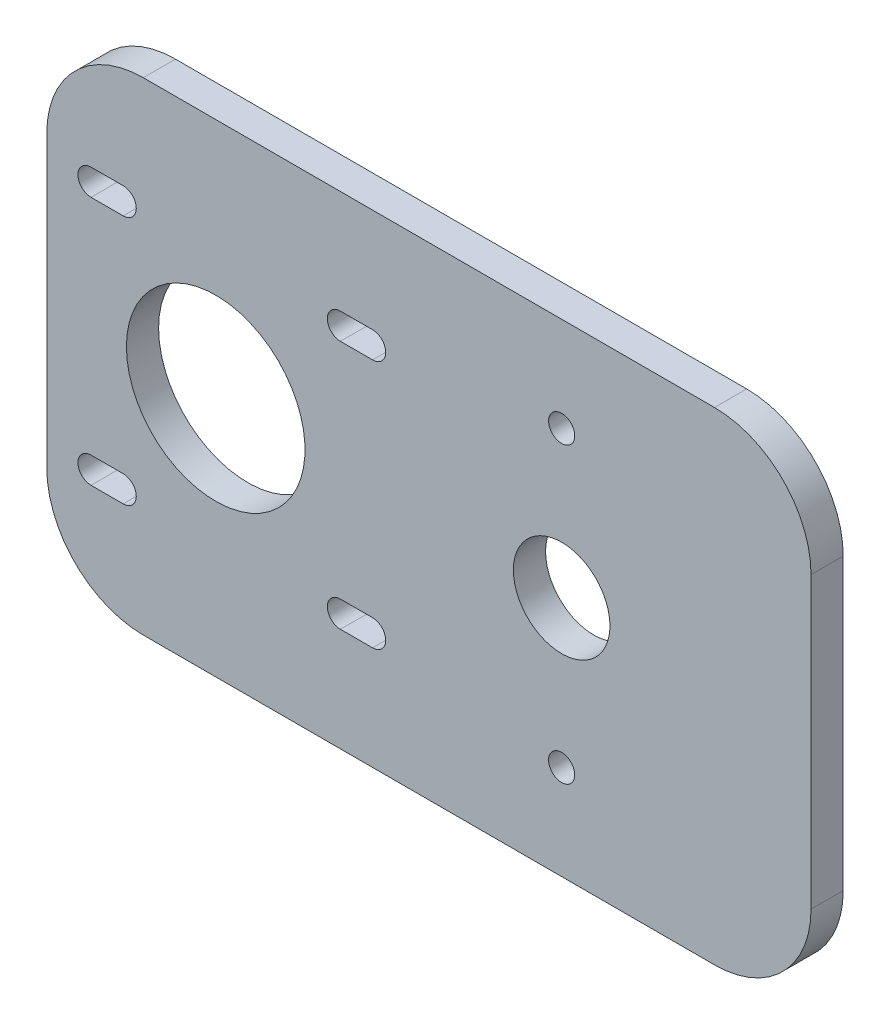
SolidWorks part; units mm, degrees
ref_plane "Alzado" through (0, 0, 0) normal (0, 0, 1) x (1, 0, 0)
ref_plane "Planta" through (0, 0, 0) normal (0, 1, 0) x (1, 0, 0)
ref_plane "Vista lateral" through (0, 0, 0) normal (1, 0, 0) x (0, 0, -1)
sketch "Croquis1" plane through (0, 0, 0) normal (0, 0, 1) x (1, 0, 0)
  line L1 (0, 0) -> (95, 0)
  line L2 (0, 0) -> (0, 60)
  line L3 (0, 60) -> (95, 60)
  line L4 (95, 0) -> (95, 60)
  dimension "D1" = 60
  dimension "D2" = 95
extrude "Saliente-Extruir1" add sketch "Croquis1" along normal blind 4
sketch "Croquis2" plane through (0, 0, 0) normal (0, 0, -1) x (-1, 0, 0)
  line L0 (0, 60) -> (0, 0) construction
  line L1 (-36.5, 45.5) -> (-40.5, 45.5) construction
  line L2 (-36.5, 43.875) -> (-40.5, 43.875)
  line L3 (-36.5, 47.125) -> (-40.5, 47.125)
  line L4 (-36.5, 14.5) -> (-40.5, 14.5) construction
  line L5 (-36.5, 12.875) -> (-40.5, 12.875)
  line L6 (-36.5, 16.125) -> (-40.5, 16.125)
  line L7 (-5.5, 14.5) -> (-9.5, 14.5) construction
  line L8 (-5.5, 12.875) -> (-9.5, 12.875)
  line L9 (-5.5, 16.125) -> (-9.5, 16.125)
  line L10 (-5.5, 45.5) -> (-9.5, 45.5) construction
  line L11 (-5.5, 43.875) -> (-9.5, 43.875)
  line L12 (-5.5, 47.125) -> (-9.5, 47.125)
  circle A3 centre (-21, 30) radius 11.1
  circle A5 centre (-64, 30) radius 6
  arc A7 (-36.5, 43.875) -> (-36.5, 47.125) centre (-36.5, 45.5) ccw
  arc A8 (-40.5, 47.125) -> (-40.5, 43.875) centre (-40.5, 45.5) ccw
  arc A9 (-36.5, 12.875) -> (-36.5, 16.125) centre (-36.5, 14.5) ccw
  arc A10 (-40.5, 16.125) -> (-40.5, 12.875) centre (-40.5, 14.5) ccw
  arc A11 (-5.5, 12.875) -> (-5.5, 16.125) centre (-5.5, 14.5) ccw
  arc A12 (-9.5, 16.125) -> (-9.5, 12.875) centre (-9.5, 14.5) ccw
  arc A13 (-5.5, 43.875) -> (-5.5, 47.125) centre (-5.5, 45.5) ccw
  arc A14 (-9.5, 47.125) -> (-9.5, 43.875) centre (-9.5, 45.5) ccw
  circle A15 centre (-64, 11.75) radius 1.625
  circle A16 centre (-64, 48.25) radius 1.625
  point P4 (-38.5, 45.5)
  point P17 (-38.5, 14.5)
  point P27 (-7.5, 14.5)
  point P34 (-7.5, 45.5)
  dimension "D1" = 3.25
  dimension "D2" = 4
  dimension "D3" = 3.25
  dimension "D4" = 4
  dimension "D5" = 22.2
  dimension "D6" = 12
  dimension "D13" = 3.25
  dimension "D14" = 3.25
  dimension "D7" = 3.25
  dimension "D8" = 4
  dimension "D9" = 3.25
  dimension "D10" = 4
  dimension "D11" = 64
  dimension "D12" = 30
  dimension "D15" = 18.25
  dimension "D16" = 18.25
extrude "Cortar-Extruir1" cut sketch "Croquis2" against normal through all
fillet "Redondeo1" radius 12 4 edges at (95, 0, 2) (95, 60, 2) (0, 0, 2) (0, 60, 2)
